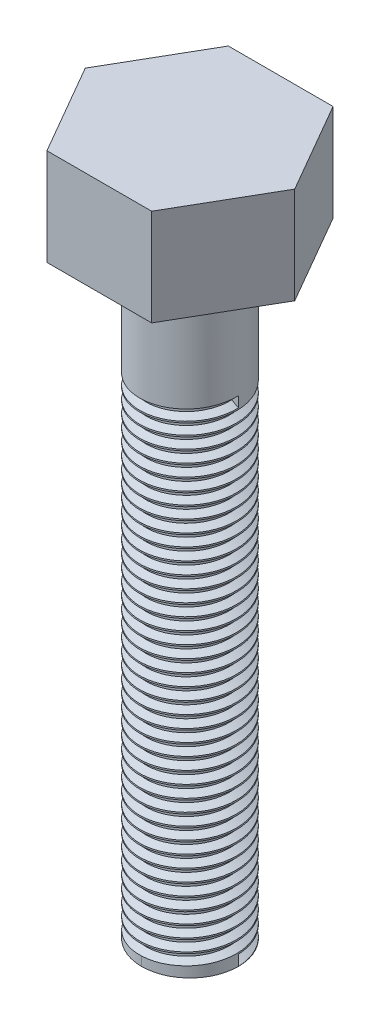
SolidWorks part; units mm, degrees
ref_plane "Front Plane" through (0, 0, 0) normal (0, 0, 1) x (1, 0, 0)
ref_plane "Top Plane" through (0, 0, 0) normal (0, 1, 0) x (1, 0, 0)
ref_plane "Right Plane" through (0, 0, 0) normal (1, 0, 0) x (0, 0, -1)
sketch "Sketch1" plane through (0, 0, 0) normal (0, 1, 0) x (1, 0, 0)
  circle A0 centre (0, 0) radius 4
  dimension "D1" = 8
extrude "Boss-Extrude1" add sketch "Sketch1" against normal blind 50
sketch "Sketch2" plane through (0, 0, 0) normal (0, 1, 0) x (1, 0, 0)
  line L1 (-8.6603, 0) -> (-4.3301, -7.5)
  line L2 (-4.3301, -7.5) -> (4.3301, -7.5)
  line L3 (4.3301, -7.5) -> (8.6603, 0)
  line L4 (8.6603, 0) -> (4.3301, 7.5)
  line L5 (4.3301, 7.5) -> (-4.3301, 7.5)
  line L6 (-4.3301, 7.5) -> (-8.6603, 0)
  circle A0 centre (0, 0) radius 7.5 construction
  dimension "D1" = 15
extrude "Boss-Extrude2" add sketch "Sketch2" along normal blind 8 contours L3 L4 L5 L6 L1 L2
thread "Thread1" pitch 1 method cut profile "Thread Profile1" start angle 0, offset 0, length 40, pitch 1, diameter 8
ref_plane "Plane1" through (4, -50, 0) normal (0, 0, 1) x (1, 0, 0)
sketch "Thread Profile1" plane through (4, -50, 0) normal (0, 0, 1) x (1, 0, 0)
  line L0 (0, 0) -> (0, 1) construction
  line L11 (0, 0) -> (0, 0.875)
  line L12 (0, 0.875) -> (-0.5413, 0.5625)
  line L13 (-0.5413, 0.5625) -> (-0.5413, 0.3125)
  line L15 (-0.5413, 0.3125) -> (0, 0)
  line L17 (-0.5413, 0.4375) -> (0, 0.4375) construction
  point P2 (0, 0)
  dimension "Pitch" = 1
  dimension "Profile_Angle" = 60
  dimension "Profile_Land" = 0.25
  dimension "Profile_Height" = 0.5413
